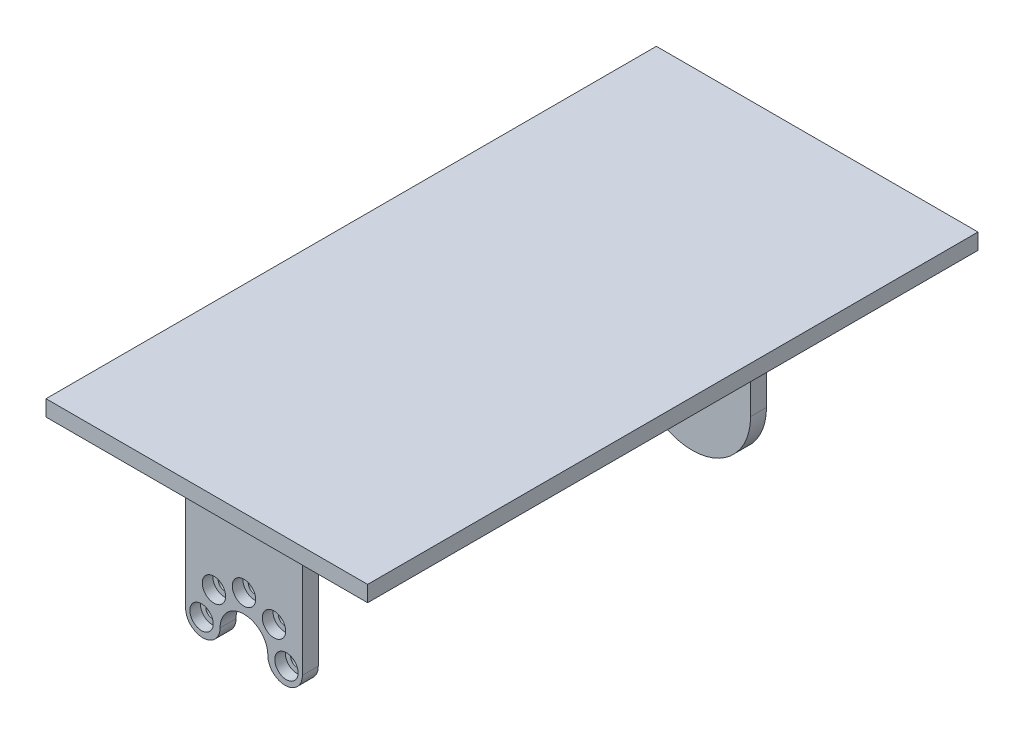
SolidWorks part; units mm, degrees
ref_plane "Plano frontal" through (0, 0, 0) normal (0, 0, 1) x (1, 0, 0)
ref_plane "Plano superior" through (0, 0, 0) normal (0, 1, 0) x (1, 0, 0)
ref_plane "Plano direito" through (0, 0, 0) normal (1, 0, 0) x (0, 0, -1)
sketch "Esboço1" plane through (0, 0, 0) normal (0, 0, 1) x (1, 0, 0)
  line L0 (11, 0) -> (11, 25)
  line L1 (11, 25) -> (-11, 25)
  line L2 (-11, 25) -> (-11, 0)
  arc A3 (11, 0) -> (4.5, 0) centre (7.75, 0) cw
  arc A8 (4.5, 0) -> (-4.5, 0) centre (0, 0) ccw
  arc A10 (-4.5, 0) -> (-11, 0) centre (-7.75, 0) cw
  dimension "D1" = 25
extrude "Ressalto-extrusão1" add sketch "Esboço1" along normal blind 3
sketch "Esboço2" plane through (0, 25, 0) normal (0, 1, 0) x (1, 0, 0)
  line L1 (-30.3, -10) -> (30.3, -10)
  line L2 (-30.3, -10) -> (-30.3, 105)
  line L3 (-30.3, 105) -> (30.3, 105)
  line L4 (30.3, -10) -> (30.3, 105)
  line L5 (11, -3) -> (-11, -3) construction
  point P7 (0, -3)
  point P8 (0, -10)
  dimension "D1" = 115
  dimension "D2" = 60.6
  dimension "D3" = 7
extrude "Ressalto-extrusão2" add sketch "Esboço2" along normal blind 3
ref_plane "Plano1" through (0, 0, -81.45) normal (0, 0, -1) x (-1, 0, 0)
sketch "Esboço3" plane through (0, 0, -81.45) normal (0, 0, -1) x (-1, 0, 0)
  line L1 (-11, 0) -> (-11, 25)
  line L2 (-11, 25) -> (11, 25)
  line L3 (11, 25) -> (11, 0)
  arc A0 (-11, 0) -> (11, 0) centre (0, 0) ccw
  dimension "D1" = 22
extrude "Ressalto-extrusão3" add sketch "Esboço3" along normal blind 3
hole_wizard "Rebaixo para SHCS M21" positions "Esboço4" profile "Esboço5" counterbore size "M2" standard "Ansi Metric" end condition up to next
sketch "Esboço4" plane through (0, 0, 3) normal (0, 0, 1) x (1, 0, 0)
  arc A0 (8.8, 0) -> (7.2, 0) centre (8, 0) ccw construction
  point P0 (8, 0)
sketch "Esboço5" plane through (8, 0, 3) normal (1, 0, 0) x (0, -1, 0)
  line L0 (0, 0) -> (0, 3)
  line L1 (0, 3) -> (1.2, 3)
  line L3 (1.2, 3) -> (1.2, 2)
  line L4 (1.2, 2) -> (2.2, 2)
  line L5 (2.2, 2) -> (2.2, 0)
  line L7 (2.2, 0) -> (0, 0)
  line L11 (0, -6.35) -> (0, 107.95) construction
  dimension "Thru Hole Dia." = 2.4
  dimension "Thru Hole Depth" = 3
  dimension "C'Bore Dia." = 4.4
  dimension "C'Bore Depth" = 2
pattern_circular "PadrãoCircular1" count 5 over 180 about axis through (0, 0, 3) along (0, 0, -1) of "Rebaixo para SHCS M21" reverse direction yes
sketch "Esboço6" plane through (0, 0, 0) normal (1, 0, 0) x (0, 0, -1)
  line L0 (-10, 25) -> (-3, 25) construction
  line L3 (-3, 25) -> (-3, 18) construction
  line L4 (-3, 0) -> (-3, 25) construction
  line L5 (-3, 18) -> (-10, 25)
rib "Nervura1" sketch "Esboço6" sketch "Esboço6" thickness 15 extrusion direction parallel to sketch draft on no parameters "D1"=15
sketch "Esboço7" plane through (0, 0, 3) normal (0, 0, 1) x (1, 0, 0)
  line L0 (-7.5, 25) -> (7.5, 25) construction
  line L1 (-5, 25) -> (5, 25)
  line L2 (-5, 25) -> (-5, 18)
  line L3 (-5, 18) -> (5, 18)
  line L4 (5, 25) -> (5, 18)
  line L5 (7.5, 18) -> (-7.5, 18) construction
  point P8 (0, 18)
  point P9 (0, 18)
  dimension "D1" = 10
extrude "Corte-extrusão1" cut sketch "Esboço7" along normal up to surface (7 mm away) up to face at (0, 21.5, 6.5)
sketch "Esboço8" plane through (0, 0, 0) normal (1, 0, 0) x (0, 0, -1)
  line L0 (0, 18) -> (7, 25)
  line L1 (0, 0) -> (0, 25) construction
  line L2 (-10, 25) -> (105, 25) construction
  line L5 (-10, 25) -> (-3, 18) construction
rib "Nervura7" sketch "Esboço8" sketch "Esboço8" thickness 15 extrusion direction parallel to sketch draft on no parameters "D1"=15
sketch "Esboço9" plane through (0, 0, 0) normal (0, 0, -1) x (-1, 0, 0)
  line L0 (-7.5, 18) -> (7.5, 18) construction
  line L1 (-5, 18) -> (5, 18)
  line L2 (-5, 18) -> (-5, 25)
  line L3 (-5, 25) -> (5, 25)
  line L4 (5, 18) -> (5, 25)
  line L5 (-11, 25) -> (-7.5, 25) construction
  point P8 (0, 18)
  point P9 (0, 18)
  dimension "D1" = 10
extrude "Corte-extrusão2" cut sketch "Esboço9" along normal up to surface up to face at (0, 21.5, -3.5)
pattern_linear "Padrão linear1" count 2 spacing 84.45 along (0, 0, -1) of "Nervura1", "Nervura7", "Corte-extrusão2", "Corte-extrusão1"
sketch "Esboço10" plane through (0, 0, -81.45) normal (0, 0, 1) x (1, 0, 0)
  circle A0 centre (0, 0) radius 2.75
  circle A2 centre (0, 0) radius 3.25 construction
  dimension "D1" = 0.5
extrude "Ressalto-extrusão4" add sketch "Esboço10" along normal offset from surface (0.6 mm away) 0.25 contours A0
hole_wizard "Rebaixo para parafuso com cabeça panela de M31" positions "Esboço11" profile "Esboço12" counterbore size "M3" standard "DIN" end condition up to next
sketch "Esboço11" plane through (0, 0, -84.45) normal (0, 0, -1) x (-1, 0, 0)
  circle A0 centre (0, 0) radius 3.25 construction
  point P0 (0, 0)
sketch "Esboço12" plane through (0, 0, -84.45) normal (1, 0, 0) x (0, 1, 0)
  line L0 (0, 0) -> (0, 3.6)
  line L1 (0, 3.6) -> (1.7, 3.6)
  line L3 (1.7, 3.6) -> (1.7, 1.5)
  line L4 (1.7, 1.5) -> (3.5, 1.5)
  line L5 (3.5, 1.5) -> (3.5, 0)
  line L7 (3.5, 0) -> (0, 0)
  line L11 (0, -6.35) -> (0, 107.95) construction
  dimension "Thru Hole Dia." = 3.4
  dimension "Thru Hole Depth" = 3.6
  dimension "C'Bore Dia." = 7
  dimension "C'Bore Depth" = 1.5
